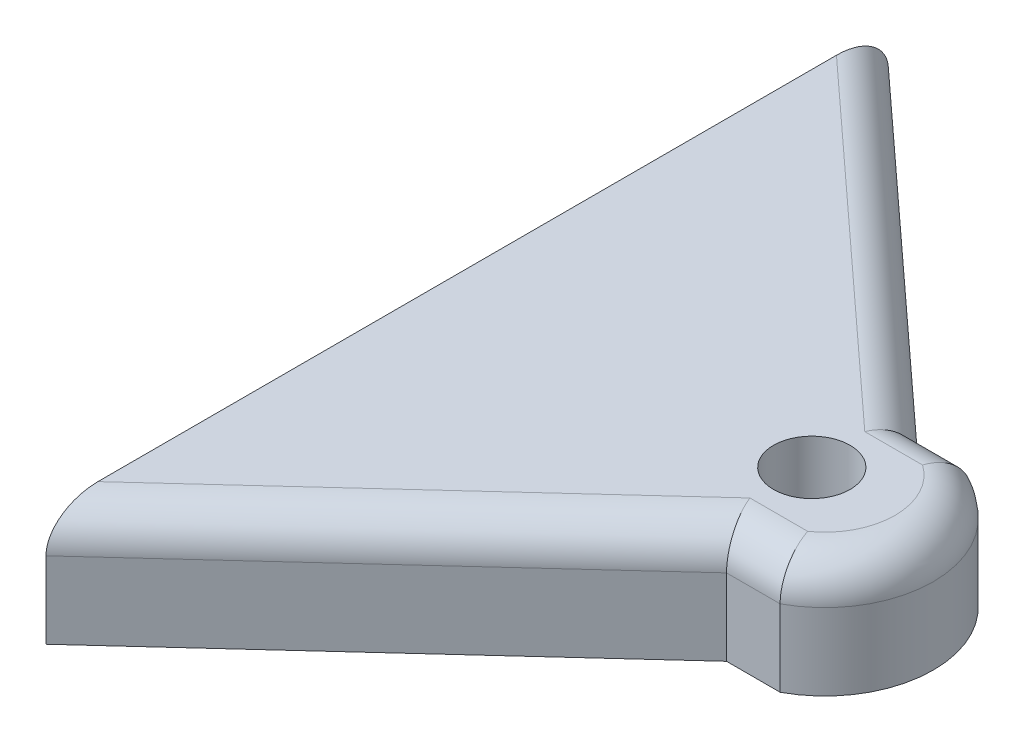
SolidWorks part; units mm, degrees
ref_plane "Front Plane" through (0, 0, 0) normal (0, 0, 1) x (1, 0, 0)
ref_plane "Top Plane" through (0, 0, 0) normal (0, 1, 0) x (1, 0, 0)
ref_plane "Right Plane" through (0, 0, 0) normal (1, 0, 0) x (0, 0, -1)
sketch "Sketch1" plane through (0, 0, 0) normal (0, 1, 0) x (1, 0, 0)
  line L3 (-6, -26.8424) -> (40.3636, 15.6576)
  line L4 (40.3636, 40.6576) -> (-6, 83.1576)
  line L5 (-6, 83.1576) -> (-6, -26.8424) construction
  line L6 (40.3636, 28.1576) -> (-6, 28.1576) construction
  line L7 (-6, 83.1576) -> (-6, -26.8424)
  line L8 (40.3636, 40.6576) -> (40.3636, 15.6576) construction
  line L9 (40.3636, 40.6576) -> (47.3636, 40.6576)
  line L11 (47.3636, 15.6576) -> (40.3636, 15.6576)
  arc A0 (47.3636, 40.6576) -> (47.3636, 15.6576) centre (40.697, 28.1576) cw
  dimension "D1" = 110
  dimension "D2" = 7
extrude "Boss-Extrude1" add sketch "Sketch1" along normal blind 15 contours L4 L7 L3 | L11 L9 L4 L3 region at (15.4037, 0, -28.1576)
sketch "Sketch2" plane through (0, 0, 0) normal (0, -1, 0) x (1, 0, 0)
  line L0 (-6, -28.1576) -> (47.5, -28.1576) construction
  line L2 (30.5, -19.6576) -> (30.5, -36.6576)
  line L4 (47.5, -19.6576) -> (47.5, -36.6576)
  line L7 (30.5, -19.6576) -> (47.5, -19.6576)
  line L8 (30.5, -36.6576) -> (47.5, -36.6576)
  line L9 (30.5, -24.1576) -> (9.5, -24.1576)
  line L10 (9.5, -24.1576) -> (9.5, -32.1576)
  line L11 (9.5, -32.1576) -> (30.5, -32.1576)
  line L13 (39, -19.6576) -> (39, -36.6576) construction
  line L14 (-6, -83.1576) -> (-6, 26.8424) construction
  point P12 (9.5, -28.1576)
  point P14 (0, 0)
  dimension "D1" = 45
  dimension "D2" = 21
  dimension "D3" = 17
  dimension "D4" = 17
  dimension "D5" = 8
extrude "Cut-Extrude2" cut sketch "Sketch2" against normal blind 6 contours L10 L11 L2 L9 | L2 L8 L4 L7 region at (39, 0, -28.1576) region at (20, 0, -28.1576)
sketch "Sketch3" plane through (0, 6, 0) normal (0, 1, 0) x (-1, 0, 0)
  line L0 (-47.5, -19.6576) -> (-30.5, -36.6576) construction
  line L1 (-30.5, -19.6576) -> (-47.5, -36.6576) construction
  circle A0 centre (-39, -28.1576) radius 5
  point P10 (-39, -28.1576)
  dimension "D1" = 10
sketch "Sketch5" plane through (-6, 0, 0) normal (-1, 0, 0) x (0, 0, 1)
  line L0 (-83.1576, 7) -> (26.8424, 7) construction
  line L4 (-53.1576, 3.5) -> (-3.1576, 3.5) construction
  line L5 (-28.1576, 3.5) -> (-28.1576, 15) construction
  line L9 (-83.1576, 15) -> (26.8424, 15) construction
  line L10 (-83.1576, 15) -> (-83.1576, 0) construction
  line L11 (26.8424, 15) -> (26.8424, 0) construction
  circle A0 centre (-53.1576, 7) radius 3.5
  circle A1 centre (-3.1576, 7) radius 3.5
  point P2 (0, 0)
  point P5 (0, 0)
  point P10 (0, 0)
  point P11 (0, 0)
  point P16 (0, 0)
  point P17 (0, 0)
  point P18 (-84.7923, 6.3167)
  point P23 (0, 0)
  point P24 (0, 0)
  point P25 (-28.1576, 15)
  dimension "D1" = 7
  dimension "D2" = 8
  dimension "D3" = 50
extrude "Cut-Extrude3" cut sketch "Sketch3" along normal through all
extrude "Boss-Extrude2" add sketch "Sketch5" along normal blind 3
fillet "Fillet2" radius 5 5 edges at (17.1818, 15, -61.9076) (43.8636, 15, -40.6576) (43.8636, 15, -15.6576) (17.1818, 15, 5.5924) (54.8636, 15, -28.1576)
